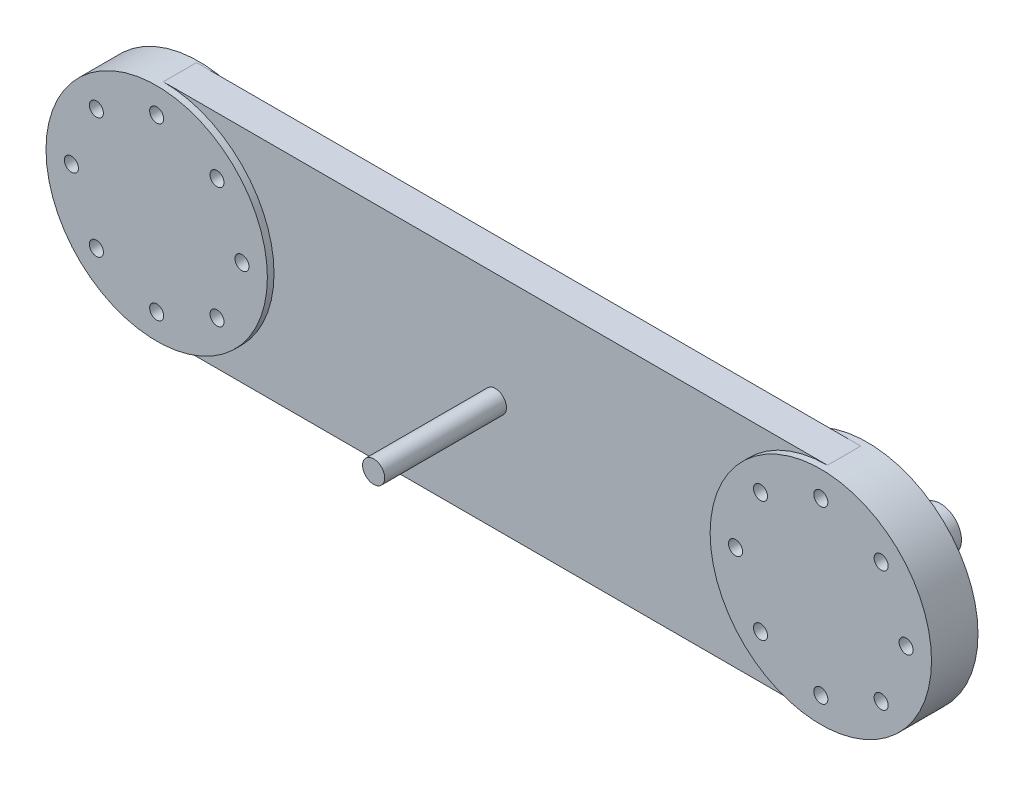
SolidWorks part; units mm, degrees
note: The reader was unsure of these and kept them because the rebuilt part matched: shared geometry of "草图1<28>", "草图1<30>", "草图1<31>", "草图1<32>", "草图1<35>", "草图1<36>", "草图1<37>", "草图1<41>", "草图1<43>".
material "3003 Alloy"
ref_plane "前视基准面" through (0, 0, 0) normal (0, 0, 1) x (1, 0, 0)
ref_plane "上视基准面" through (0, 0, 0) normal (0, 1, 0) x (1, 0, 0)
ref_plane "右视基准面" through (0, 0, 0) normal (1, 0, 0) x (0, 0, -1)
sketch "草图1" plane through (0, 0, 0) normal (0, 0, 1) x (1, 0, 0)
  line L0 (0, 100) -> (-300, 0) construction
  line L5 (0, 0) -> (-300, 0)
  line L6 (0, 0) -> (0, 100)
  line L7 (0, 100) -> (-300, 100)
  line L8 (-300, 0) -> (-300, 100)
  line L9 (-300, 100) -> (0, 0) construction
  line L10 (-300, 50) -> (-250, 50)
  line L11 (-250, 50) -> (-300, 100) construction
  line L12 (-300, 50) -> (-264.6447, 85.3553) construction
  line L13 (-300, 50) -> (-335.3553, 14.6447)
  line L14 (-150, 50) -> (-150, 0)
  line L15 (-264.6447, 85.3553) -> (-335.3553, 85.3553) construction
  line L16 (-264.6447, 85.3553) -> (-264.6447, 14.6447) construction
  line L17 (-264.6447, 14.6447) -> (-335.3553, 14.6447) construction
  line L18 (-335.3553, 85.3553) -> (-335.3553, 14.6447) construction
  line L19 (-150, 0) -> (-150, 100) construction
  line L20 (6.25, 50) -> (8.25, 50)
  line L21 (6.25, 50) -> (8.25, 50)
  line L22 (6.25, 47.9959) -> (6.25, 52.0041)
  line L23 (8.25, 47.9959) -> (8.25, 52.0041)
  line L24 (6.25, 52.0041) -> (8.25, 52.0041)
  line L25 (6.25, 52.0041) -> (5.92, 52.0041)
  line L26 (6.25, 52.0041) -> (6.25, 50)
  line L27 (6.25, 52.0041) -> (6.25, 47.9959)
  line L28 (6.25, 52.0041) -> (5.137, 52.0041)
  line L29 (6.25, 50) -> (5.137, 50)
  line L30 (5.137, 52.0041) -> (5.137, 47.9959)
  line L31 (6.25, 47.9959) -> (5.137, 47.9959)
  line L32 (6.25, 47.9959) -> (8.25, 47.9959)
  circle A6 centre (0, 50) radius 50
  circle A7 centre (0, 50) radius 25
  circle A8 centre (-300, 50) radius 50
  circle A9 centre (-300, 50) radius 25
  circle A12 centre (-150, 50) radius 5
  circle A14 centre (-261.4697, 50) radius 3.175
  circle A23 centre (-38.5303, 50) radius 3.175
  circle A30 centre (-272.7549, 22.7549) radius 3.175
  circle A31 centre (-300, 11.4697) radius 3.175
  circle A32 centre (-327.2451, 22.7549) radius 3.175
  circle A33 centre (-338.5303, 50) radius 3.175
  circle A34 centre (-327.2451, 77.2451) radius 3.175
  circle A35 centre (-300, 88.5303) radius 3.175
  circle A36 centre (-272.7549, 77.2451) radius 3.175
  circle A37 centre (-27.2451, 77.2451) radius 3.175
  circle A38 centre (-27.2451, 77.2451) radius 3.175
  circle A39 centre (0, 88.5303) radius 3.175
  circle A40 centre (27.2451, 77.2451) radius 3.175
  circle A41 centre (38.5303, 50) radius 3.175
  circle A42 centre (27.2451, 22.7549) radius 3.175
  circle A43 centre (0, 11.4697) radius 3.175
  circle A44 centre (-27.2451, 22.7549) radius 3.175
  circle A45 centre (0, 50) radius 6.25
  circle A46 centre (0, 50) radius 9.525
  point P70 (-300, 50)
  point P87 (0, 50)
  dimension "D1" = 100
  dimension "D2" = 300
  dimension "D3" = 50
  dimension "D4" = 50
  dimension "D5" = 10
  dimension "D6" = 2
  dimension "D7" = 6.35
  dimension "D8" = 12.5
  dimension "D9" = 19.05
extrude "凸台-拉伸18" add sketch "草图1" along normal blind 13 contours A8 | A6
extrude "凸台-拉伸21" add sketch "草图1<28>" along normal blind 15 contours L5 L8 L7 L6
sketch "草图1<28>" plane through (0, 0, 0) normal (0, 0, 1) x (1, 0, 0) same geometry as "草图1"
extrude "凸台-拉伸22" add sketch "草图1<30>" along normal blind 70 contours A12
sketch "草图1<30>" plane through (0, 0, 0) normal (0, 0, 1) x (1, 0, 0) same geometry as "草图1"
extrude "切除-拉伸2" cut sketch "草图1<31>" along normal blind 41 contours A8
sketch "草图1<31>" plane through (0, 0, 0) normal (0, 0, 1) x (1, 0, 0) same geometry as "草图1"
extrude "凸台-拉伸23" add sketch "草图1<32>" along normal blind 18 and the other way blind 1 contours A8
sketch "草图1<32>" plane through (0, 0, 0) normal (0, 0, 1) x (1, 0, 0) same geometry as "草图1"
extrude "切除-拉伸5" cut sketch "草图1<35>" against normal blind 69 and the other way blind 130
sketch "草图1<35>" plane through (0, 0, 0) normal (0, 0, 1) x (1, 0, 0) same geometry as "草图1"
extrude "切除-拉伸6" cut sketch "草图1<36>" along normal blind 34 contours A6
sketch "草图1<36>" plane through (0, 0, 0) normal (0, 0, 1) x (1, 0, 0) same geometry as "草图1"
extrude "凸台-拉伸24" add sketch "草图1<37>" against normal blind 3 and the other way blind 18 contours A6
sketch "草图1<37>" plane through (0, 0, 0) normal (0, 0, 1) x (1, 0, 0) same geometry as "草图1"
extrude "切除-拉伸7" cut sketch "草图1<41>" along normal blind 87 and the other way blind 98 contours A36 | L8 A35 | L8 A35 | A34 | A33 | L13 A32 | L8 A31 | A30 | L10 A14 | L10 A14 | A44 | A23 | A37 | A39 L6 | A39 L6 | A40 | A42 | A41 | A43 L6 | A43 L6
sketch "草图1<41>" plane through (0, 0, 0) normal (0, 0, 1) x (1, 0, 0) same geometry as "草图1"
sketch "Sketch1" plane through (0, 0, -3) normal (0, 0, -1) x (-1, 0, 0)
  line L0 (-50, 50) -> (50, 50) construction
  line L1 (0, 0) -> (0, 100) construction
  circle A0 centre (0, 50) radius 50 construction
  arc A1 (0, 0) -> (0, 100) centre (0, 50) ccw construction
  point P11 (0, 50)
ref_point "RotatioanAxixCentre"
sketch "Sketch2" plane through (0, 100, 0) normal (0, 1, 0) x (1, 0, 0)
  line L0 (0, -18) -> (0, 3)
  line L2 (50, 3) -> (-50, 3) construction
  point P3 (0, -7.5)
  dimension "D1" = 10.5
extrude "the extended shaft connecter" add sketch "草图1<43>" against normal blind 36 contours L6 A46 A45 L25 L24 L23 L32 L31 | L6 A46 A45
sketch "草图1<43>" plane through (0, 0, 0) normal (0, 0, 1) x (1, 0, 0) same geometry as "草图1"
ref_plane "基准面1" through (5.92, 52.0041, -36) normal (-0.3207, 0.9472, 0) x (0.9472, 0.3207, 0)
sketch "草图3" plane through (0, 0, 0) normal (1, 0, 0) x (0, 0, -1)
  line L0 (25, 50) -> (25, 59.525)
  line L1 (36, 59.525) -> (3, 59.525) construction
  line L2 (25, 59.525) -> (32, 59.525)
  line L3 (32, 59.525) -> (32, 50)
  circle A0 centre (32, 50) radius 1.5875
  circle A1 centre (25, 50) radius 1.5875
  dimension "D1" = 3.175
  dimension "D2" = 3.175
extrude "切除-拉伸8" cut sketch "草图3" against normal blind 31
sketch "草图5" plane through (0, 0, 0) normal (0, 1, 0) x (1, 0, 0)
  circle A0 centre (0, 32) radius 1.5875
  circle A1 centre (0, 25) radius 1.5875
  dimension "D1" = 3.175
  dimension "D2" = 3.175
extrude "screw_holes2" cut sketch "草图5" along normal up to vertex
sketch "Sketch3" plane through (0, 0, 18) normal (0, 0, 1) x (1, 0, 0)
  line L0 (-300, 50) -> (-300, 100) construction
  line L1 (-300, 50) -> (-250, 50) construction
  circle A0 centre (-300, 50) radius 50 construction
  point P7 (-300, 50)
